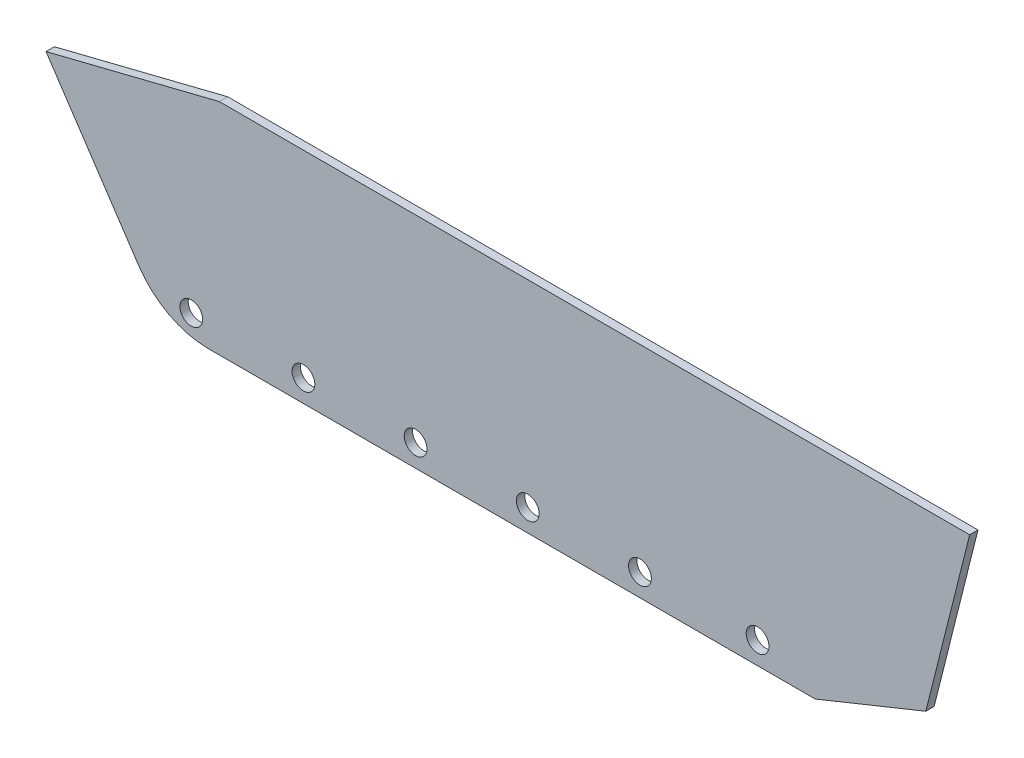
SolidWorks part; units mm, degrees
material "5052-H32"
ref_plane "Front Plane" through (0, 0, 0) normal (0, 0, 1) x (1, 0, 0)
ref_plane "Top Plane" through (0, 0, 0) normal (0, 1, 0) x (1, 0, 0)
ref_plane "Right Plane" through (0, 0, 0) normal (1, 0, 0) x (0, 0, -1)
sketch "Sketch1" plane through (0, 0, 0) normal (0, 0, 1) x (1, 0, 0)
  line L1 (428.1206, 33.3333) -> (428.1206, 28.5708)
  line L3 (428.1206, 28.5708) -> (0, 28.5708)
  line L4 (0, 28.5708) -> (-98.8794, 3.851)
  line L6 (-98.8794, 3.851) -> (-31.8794, -96.649)
  line L7 (428.1206, 28.5708) -> (403.1206, -71.149)
  line L9 (403.1206, -71.149) -> (366, -96.649)
  line L10 (-31.8794, -96.649) -> (366, -96.649)
  circle A0 centre (-16, -83.899) radius 6.5
  circle A1 centre (48, -83.899) radius 6.5
  circle A2 centre (112, -83.899) radius 6.5
  circle A3 centre (176, -83.899) radius 6.5
  circle A4 centre (240, -83.899) radius 6.5
  circle A5 centre (307.1206, -83.899) radius 6.5
  point P0 (-48.8794, -71.149)
  point P2 (-31.8794, -96.649)
  point P8 (48, -83.899)
  point P9 (403.1206, -71.149)
  dimension "D2" = 64
  dimension "D4" = 64
  dimension "D1" = 25.5
  dimension "D3" = 75
  dimension "D5" = 25
  dimension "D6" = 96
  dimension "D7" = 527
  dimension "D9" = 64
  dimension "D10" = 64
  dimension "D11" = 64
  dimension "D12" = 123.69
  dimension "D13" = 12.75
extrude "Boss-Extrude1" add sketch "Sketch1" along normal blind 4.7625 contours L3 L4 L6 L10 L9 L7
extrude "Cut-Extrude1" cut sketch "Sketch1<4>" along normal through all contours A0 | A1 | A2 | A3 | A4 | A5 region at (-16, -83.899, 0)
sketch "Sketch1<4>" plane through (0, 0, 0) normal (0, 0, 1) x (1, 0, 0) same geometry as "Sketch1"
sketch "Sketch2" plane through (0, 0, 0) normal (0, 0, -1) x (-1, 0, 0)
  circle A0 centre (-275.1206, -83.899) radius 6.5
  circle A2 centre (-233.5603, -132.5687) radius 6.5
  circle A3 centre (-192, -83.899) radius 6.5
  circle A4 centre (-128, -83.899) radius 6.5
  circle A5 centre (-64, -83.899) radius 6.5
  circle A6 centre (0, -83.899) radius 6.5
  dimension "D2" = 0
  dimension "D3" = 64
  dimension "D4" = 64
  dimension "D5" = 64
  dimension "D6" = 64
  dimension "D7" = 64
  dimension "D1" = 32
sketch "Sketch5" plane through (0, 0, 0) normal (0, 0, -1) x (-1, 0, 0)
  line L0 (48.8794, -71.149) -> (-14.2353, -96.649)
  line L1 (31.8794, -96.649) -> (-366, -96.649) construction
  line L2 (-14.2353, -96.649) -> (31.8794, -96.649)
  line L3 (31.8794, -96.649) -> (48.8794, -71.149)
  line L6 (-366, -96.649) -> (-403.1206, -71.149)
  line L7 (-403.1206, -71.149) -> (-352, -71.149)
  line L9 (-352, -71.149) -> (-326.5, -96.649)
  line L11 (-366, -96.649) -> (-326.5, -96.649)
  dimension "D1" = 22
  dimension "D2" = 45
extrude "Cut-Extrude2" [suppressed] cut sketch "Sketch5" against normal up to next
sketch "Sketch6" plane through (0, 0, 4.7625) normal (0, 0, 1) x (1, 0, 0)
  line L0 (-48.8794, -71.149) -> (14.2353, -96.649)
  line L1 (-31.8794, -96.649) -> (366, -96.649) construction
  line L2 (14.2353, -96.649) -> (-31.8794, -96.649)
  line L3 (-31.8794, -96.649) -> (-48.8794, -71.149)
  dimension "D1" = 158
fillet "Fillet1" radius 48 1 edges at (-31.8794, -96.649, 2.3813)
sketch "Sketch7" plane through (0, 0, 4.7625) normal (0, 0, 1) x (1, 0, 0)
  line L0 (403.1206, -71.149) -> (340.0059, -96.649)
  line L1 (-31.8794, -96.649) -> (366, -96.649) construction
  line L2 (340.0059, -96.649) -> (366, -96.649)
  line L3 (366, -96.649) -> (403.1206, -71.149)
  dimension "D1" = 22
extrude "Cut-Extrude3" cut sketch "Sketch7" against normal blind 10
